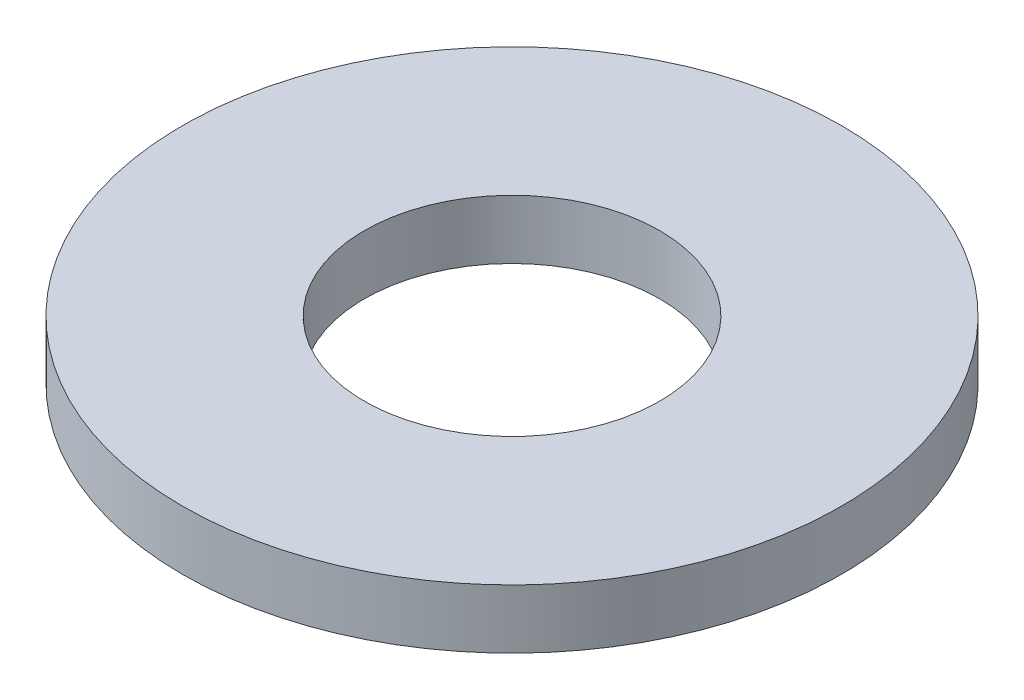
SolidWorks part; units mm, degrees
ref_plane "Front Plane" through (0, 0, 0) normal (0, 0, 1) x (1, 0, 0)
ref_plane "Top Plane" through (0, 0, 0) normal (0, 1, 0) x (1, 0, 0)
ref_plane "Right Plane" through (0, 0, 0) normal (1, 0, 0) x (0, 0, -1)
sketch "Sketch1" plane through (0, 0, 0) normal (0, 1, 0) x (1, 0, 0)
  circle A0 centre (0, 0) radius 72.5
  dimension "FLANGE_OD" = 145
extrude "Boss-Extrude1" add sketch "Sketch1" along normal blind 13
sketch "Sketch2" plane through (0, 0, 0) normal (0, 1, 0) x (1, 0, 0)
  circle A0 centre (0, 0) radius 32.5
  dimension "BORE_D" = 65
extrude "Cut-Extrude1" cut sketch "Sketch2" along normal through all
sketch "Sketch3" plane through (0, 13, 0) normal (0, 1, 0) x (1, 0, 0)
  circle A0 centre (0, 0) radius 22.0867 construction
  circle A1 centre (-22.0867, 0) radius 4.1568
  dimension "BOLT_D" = 8.3137
  dimension "BOLT_PCD" = 44.1734
extrude "Cut-Extrude2" cut sketch "Sketch3" against normal blind 11.567 rebuild error yes
pattern_circular "CirPattern1" count 3 over 360 rebuild error yes
